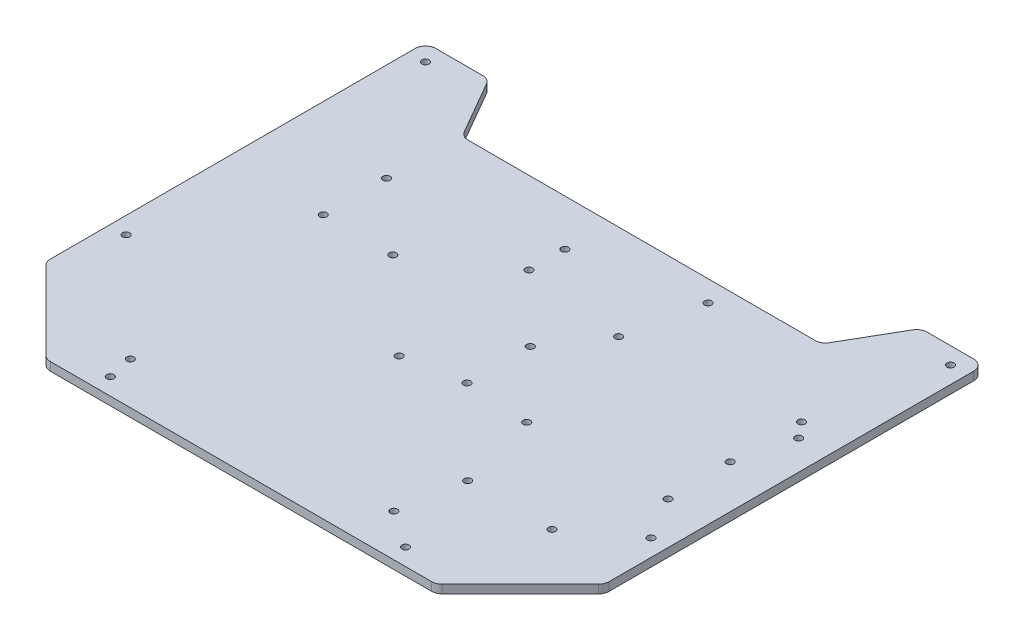
SolidWorks part; units mm, degrees
material "Acier non allié"
ref_plane "Front" through (0, 0, 0) normal (0, 0, 1) x (1, 0, 0)
ref_plane "Top" through (0, 0, 0) normal (0, 1, 0) x (1, 0, 0)
ref_plane "Right" through (0, 0, 0) normal (1, 0, 0) x (0, 0, -1)
sketch "Main scetch" plane through (0, 0, 0) normal (0, 1, 0) x (1, 0, 0)
  line L1 (0, 0) -> (132.5, 0) construction
  line L2 (0, 0) -> (0, 220) construction
  line L3 (0, 220) -> (132.5, 220) construction
  line L4 (132.5, 0) -> (132.5, 220) construction
  line L13 (-92.5, 0) -> (92.5, 0)
  line L14 (92.5, 0) -> (132.5, 40)
  line L15 (132.5, 40) -> (132.5, 220)
  line L16 (132.5, 220) -> (102.5, 220)
  line L17 (102.5, 220) -> (85.1795, 190)
  line L18 (85.1795, 190) -> (-85.1795, 190)
  line L19 (-102.5, 220) -> (-85.1795, 190)
  line L20 (-132.5, 220) -> (-102.5, 220)
  line L21 (-132.5, 40) -> (-132.5, 220)
  line L22 (-92.5, 0) -> (-132.5, 40)
  point P11 (0, 190)
  dimension "132.5" = 132.5
  dimension "D2" = 220
  dimension "D1" = 40
  dimension "D3" = 40
  dimension "D4" = 30
  dimension "D5" = 60
  dimension "D6" = 30
extrude "Main extrusion" add sketch "Main scetch" along normal blind 4
fillet "Congé1" radius 5 10 edges at (-132.5, 2, -40) (-92.5, 2, 0) (92.5, 2, 0) (132.5, 2, -40) (132.5, 2, -220) (102.5, 2, -220) (85.1795, 2, -190) (-85.1795, 2, -190) (-102.5, 2, -220) (-132.5, 2, -220)
sketch "Esquisse1" plane through (0, 4, 0) normal (0, 1, 0) x (1, 0, 0)
  line L0 (0, 0) -> (0, 218.5516) construction
  line L1 (132.5, 42.0711) -> (132.5, 215) construction
  line L2 (127.5, 220) -> (105.3868, 220) construction
  line L3 (-90.4289, 0) -> (90.4289, 0) construction
  circle A0 centre (70, 8) radius 1
  circle A1 centre (124.5, 70) radius 1
  circle A2 centre (124.5, 212) radius 1
  circle A3 centre (-124.5, 212) radius 1
  circle A4 centre (-124.5, 70) radius 1
  circle A5 centre (-70, 8) radius 1
  dimension "D1" = 2
  dimension "D2" = 2
  dimension "D3" = 2
  dimension "D4" = 8
  dimension "D5" = 8
  dimension "D6" = 8
  dimension "D7" = 8
  dimension "D8" = 70
  dimension "D9" = 70
extrude "Enlèv. mat.-Extru.1" cut sketch "Esquisse1" against normal through all
hole_wizard "Dégagement M31" positions "Esquisse2" profile "Esquisse3" hole size "M3" standard "ISO" end condition through all
sketch "Esquisse2" plane through (0, 4, 0) normal (0, 1, 0) x (1, 0, 0)
  point P0 (-124.5, 212)
  point P3 (-124.5, 70)
  point P6 (-70, 8)
  point P9 (70, 8)
  point P12 (124.5, 70)
  point P15 (124.5, 212)
sketch "Esquisse3" plane through (-124.5, 4, -212) normal (1, 0, 0) x (0, 0, 1)
  line L0 (0, 0) -> (0, 4)
  line L1 (0, 4) -> (1.7, 4)
  line L2 (1.7, 4) -> (1.7, 0)
  line L5 (1.7, 0) -> (0, 0)
  line L11 (0, -6.35) -> (0, 107.95) construction
  dimension "Diamètre du perçage jusqu'au prochain" = 3.4
  dimension "Profondeur du perçage jusqu'au prochain" = 4
sketch "Esquisse4" plane through (0, 4, 0) normal (0, 1, 0) x (1, 0, 0)
  line L0 (-132.5, 215) -> (-132.5, 42.0711) construction
  line L1 (-105.3868, 220) -> (-127.5, 220) construction
  line L2 (82.2927, 190) -> (-82.2927, 190) construction
  line L3 (132.5, 42.0711) -> (132.5, 215) construction
  line L4 (-90.4289, 0) -> (90.4289, 0) construction
  line L5 (127.5, 220) -> (105.3868, 220) construction
  circle A0 centre (-86, 125) radius 1
  circle A1 centre (-86, 155) radius 1
  circle A2 centre (-53, 125) radius 1
  circle A3 centre (-14.5, 151.1) radius 1
  circle A4 centre (-14.5, 168.1) radius 1
  circle A5 centre (41.5, 180) radius 1
  circle A6 centre (34.12, 145) radius 1
  circle A7 centre (112.5, 153.32) radius 1
  circle A8 centre (118.5, 146) radius 1
  circle A9 centre (112, 120) radius 1
  circle A10 centre (112.5, 90) radius 1
  circle A11 centre (17.2, 120) radius 1
  circle A12 centre (17.2, 90) radius 1
  circle A13 centre (47.5, 88) radius 1
  circle A14 centre (57.5, 50) radius 1
  circle A15 centre (97.5, 50) radius 1
  circle A16 centre (52.5, 20) radius 1
  circle A17 centre (-10, 85) radius 1
  circle A18 centre (-72.5, 20) radius 1
  dimension "D1" = 2
  dimension "D4" = 2
  dimension "D6" = 2
  dimension "D8" = 2
  dimension "D11" = 2
  dimension "D13" = 2
  dimension "D16" = 2
  dimension "D19" = 2
  dimension "D24" = 2
  dimension "D25" = 2
  dimension "D28" = 2
  dimension "D30" = 2
  dimension "D32" = 2
  dimension "D36" = 2
  dimension "D37" = 2
  dimension "D40" = 2
  dimension "D48" = 2
  dimension "D49" = 2
  dimension "D50" = 2
  dimension "D2" = 46.5
  dimension "D3" = 95
  dimension "D5" = 65
  dimension "D7" = 79.5
  dimension "D9" = 38.9
  dimension "D10" = 118
  dimension "D12" = 21.9
  dimension "D14" = 174
  dimension "D15" = 10
  dimension "D17" = 166.62
  dimension "D18" = 45
  dimension "D20" = 20
  dimension "D21" = 66.68
  dimension "D22" = 14
  dimension "D23" = 74
  dimension "D26" = 20.5
  dimension "D27" = 100
  dimension "D29" = 30
  dimension "D31" = 115.3
  dimension "D33" = 115.3
  dimension "D34" = 132
  dimension "D35" = 85
  dimension "D38" = 50
  dimension "D39" = 75
  dimension "D41" = 35
  dimension "D42" = 80
  dimension "D43" = 20
  dimension "D44" = 20
  dimension "D45" = 205
  dimension "D46" = 85
  dimension "D47" = 142.5
extrude "Enlèv. mat.-Extru.2" cut sketch "Esquisse4" against normal through all
hole_wizard "Dégagement M32" positions "Esquisse5" profile "Esquisse6" hole size "M3" standard "ISO" end condition through all
sketch "Esquisse5" plane through (0, 4, 0) normal (0, 1, 0) x (1, 0, 0)
  point P0 (-86, 155)
  point P3 (-86, 125)
  point P6 (-53, 125)
  point P9 (17.2, 120)
  point P12 (-14.5, 151.1)
  point P15 (-14.5, 168.1)
  point P18 (34.12, 145)
  point P21 (41.5, 180)
  point P24 (112.5, 153.32)
  point P27 (118.5, 146)
  point P30 (112, 120)
  point P33 (112.5, 90)
  point P36 (47.5, 88)
  point P39 (17.2, 90)
  point P42 (57.5, 50)
  point P45 (97.5, 50)
  point P48 (-10, 85)
  point P51 (-72.5, 20)
  point P54 (52.5, 20)
sketch "Esquisse6" plane through (-86, 4, -155) normal (1, 0, 0) x (0, 0, 1)
  line L0 (0, 0) -> (0, 4)
  line L1 (0, 4) -> (1.7, 4)
  line L2 (1.7, 4) -> (1.7, 0)
  line L5 (1.7, 0) -> (0, 0)
  line L11 (0, -6.35) -> (0, 107.95) construction
  dimension "Diamètre du perçage jusqu'au prochain" = 3.4
  dimension "Profondeur du perçage jusqu'au prochain" = 4
equation "\"WIDTH\"= 300mm'Total width of the robot"
equation "\"LENGTH\"= 220mm'Total length of the robot"
equation "\"D2@Main scetch\" = \"LENGTH\""
equation "\"CUT_DEPTH\"= 45mm'Depth of the cut on the edges of the plate"
equation "\"Plate_th\"= 3mm'Thickness of the plate"
equation "\"D1\"= \"Plate_th\""
equation "\"D47@Esquisse4\"=(80+205)/2"
